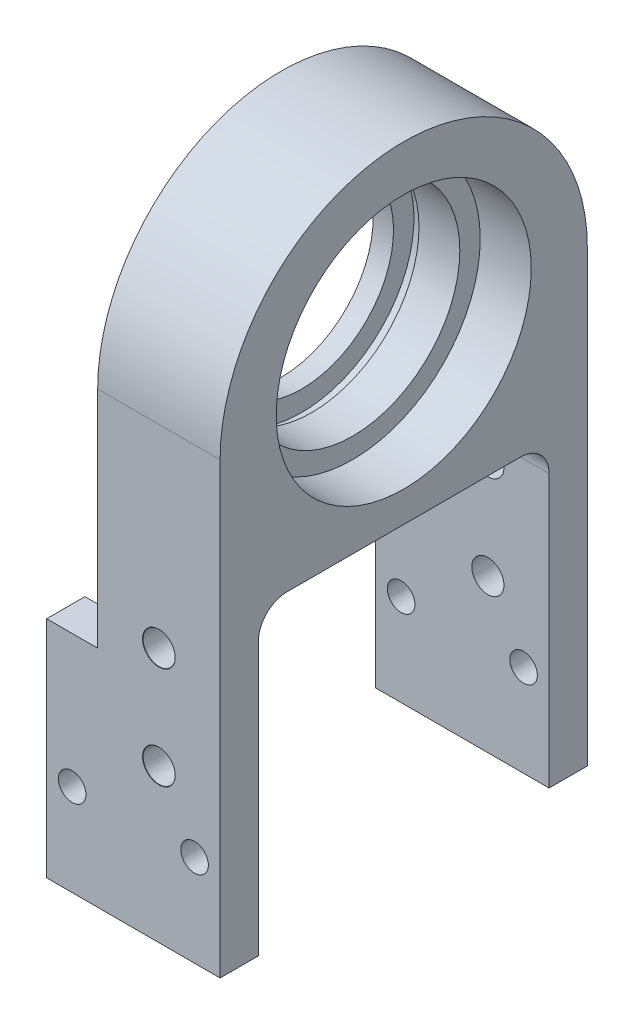
SolidWorks part; units mm, degrees
material "6061 Alloy"
ref_plane "Front Plane" through (0, 0, 0) normal (0, 0, 1) x (1, 0, 0)
ref_plane "Top Plane" through (0, 0, 0) normal (0, 1, 0) x (1, 0, 0)
ref_plane "Right Plane" through (0, 0, 0) normal (1, 0, 0) x (0, 0, -1)
sketch "Sketch1" plane through (0, 0, 0) normal (0, 0, 1) x (1, 0, 0)
  line L0 (0, 0) -> (17, 0)
  line L1 (17, 0) -> (17, 29)
  line L3 (17, 29) -> (17, 62)
  line L4 (17, 62) -> (5, 62)
  line L5 (5, 62) -> (5, 22)
  line L6 (5, 22) -> (0, 22)
  line L7 (0, 22) -> (0, 0)
  dimension "D1" = 17
  dimension "D2" = 62
  dimension "D3" = 22
  dimension "D4" = 12
extrude "Boss-Extrude1" add sketch "Sketch1" along normal blind 36
sketch "Sketch2" plane through (17, 0, 0) normal (1, 0, 0) x (0, 0, -1)
  line L0 (-18, 62) -> (-18, 12.1467) construction
  line L1 (-36, 62) -> (0, 62) construction
  circle A0 centre (-18, 45) radius 10.5
  dimension "D1" = 21
  dimension "D2" = 17
extrude "Cut-Extrude1" cut sketch "Sketch2" against normal through all
sketch "Sketch3" plane through (17, 0, 0) normal (1, 0, 0) x (0, 0, -1)
  line L0 (-36, 0) -> (0, 0) construction
  line L1 (-32.25, 0) -> (-3.75, 0)
  line L2 (-32.25, 0) -> (-32.25, 29.5)
  line L3 (-32.25, 29.5) -> (-3.75, 29.5)
  line L4 (-3.75, 0) -> (-3.75, 29.5)
  line L6 (-18, 0) -> (-18, 45) construction
  dimension "D1" = 28.5
  dimension "D2" = 29.5
extrude "Cut-Extrude2" cut sketch "Sketch3" against normal through all
sketch "Sketch6" plane through (5, 0, 0) normal (-1, 0, 0) x (0, 0, 1)
  circle A0 centre (18, 45) radius 10.5 construction
  circle A1 centre (18, 45) radius 10.5
  circle A2 centre (18, 45) radius 9
  dimension "D1" = 1.5
extrude "Boss-Extrude2" add sketch "Sketch6" against normal blind 2
sketch "Sketch10" plane through (5, 0, 0) normal (-1, 0, 0) x (0, 0, 1)
  circle A0 centre (18, 45) radius 11
  circle A1 centre (18, 45) radius 15
  dimension "D1" = 22
  dimension "D2" = 30
extrude "Cut-Extrude4" cut sketch "Sketch10" against normal blind 0.6
sketch "Sketch11" plane through (17, 0, 0) normal (1, 0, 0) x (0, 0, -1)
  circle A0 centre (-18, 45) radius 12.5
  dimension "D1" = 25
extrude "Cut-Extrude5" cut sketch "Sketch11" against normal blind 5
sketch "Sketch14" plane through (0, 0, 36) normal (0, 0, 1) x (1, 0, 0)
  line L0 (2.5, 9) -> (14.5, 9)
  line L3 (8.5, 9) -> (8.5, 0)
  line L4 (0, 0) -> (17, 0) construction
  line L6 (17, 32.5) -> (17, 57.5) construction
  line L7 (17, 32.5) -> (17, 57.5) construction
  point P0 (14.5, 9)
  point P2 (2.5, 9)
  point P25 (17, 45)
  dimension "D1" = 36
  dimension "D2" = 12
hole_wizard "M2.5 Clearance Hole1" positions "Sketch14" profile "Sketch13" hole size "M2.5" standard "DIN" end condition through all
sketch "Sketch13" plane through (14.5, 9, 36) normal (1, 0, 0) x (0, -1, 0)
  line L0 (0, 0) -> (0, 36)
  line L1 (0, 36) -> (1.35, 36)
  line L2 (1.35, 36) -> (1.35, 0)
  line L5 (1.35, 0) -> (0, 0)
  line L11 (0, -6.35) -> (0, 107.95) construction
  dimension "Thru Hole Dia." = 2.7
  dimension "Thru Hole Depth" = 36
sketch "Sketch15" plane through (0, 0, 0) normal (0, 0, -1) x (-1, 0, 0)
  line L0 (-14.5, 9) -> (-14.5, 3) construction
  line L1 (-13.15, 9) -> (-13.15, 3)
  line L2 (-15.85, 9) -> (-15.85, 3)
  line L3 (-2.5, 9) -> (-2.5, 3) construction
  line L4 (-1.15, 9) -> (-1.15, 3)
  line L5 (-3.85, 9) -> (-3.85, 3)
  arc A0 (-13.15, 9) -> (-15.85, 9) centre (-14.5, 9) ccw
  arc A1 (-15.85, 3) -> (-13.15, 3) centre (-14.5, 3) ccw
  arc A2 (-1.15, 9) -> (-3.85, 9) centre (-2.5, 9) ccw
  arc A3 (-3.85, 3) -> (-1.15, 3) centre (-2.5, 3) ccw
  circle A4 centre (-14.5, 9) radius 1.35 construction
  point P3 (-14.5, 6)
  point P8 (-2.5, 6)
  dimension "D1" = 6
extrude "Cut-Extrude6" [suppressed] cut sketch "Sketch15" against normal through all
sketch "Sketch16" plane through (0, 0, 0) normal (0, 0, -1) x (-1, 0, 0)
  line L0 (0, 22) -> (-5, 32)
  line L1 (-5, 62) -> (-5, 22) construction
  dimension "D1" = 10
rib "Rib6" [suppressed] sketch "Sketch16" sketch "Sketch16" thickness 3.75 extrusion direction parallel to sketch draft on no parameters "D1"=3.75
sketch "Sketch17" plane through (17, 0, 0) normal (1, 0, 0) x (0, 0, -1)
  line L1 (-36, 62) -> (0, 62)
  line L2 (-36, 62) -> (-36, 45)
  line L3 (-36, 45) -> (0, 45)
  line L4 (0, 62) -> (0, 45)
  circle A0 centre (-18, 45) radius 18
  line M9 (0, 0) -> (0, 62)
  line M10 (0, 62) -> (-36, 62)
  line M11 (-36, 62) -> (-36, 0)
extrude "Cut-Extrude7" cut sketch "Sketch17" against normal through all contours A0 M10 M11 | A0 M9 M10 region at (17, 58.082, 32.7544) region at (17, 58.082, 3.2456)
sketch "Sketch18" plane through (7, 0, 0) normal (1, 0, 0) x (0, 0, -1)
  circle A0 centre (-18, 45) radius 9 construction
  circle A1 centre (-18, 45) radius 9
  circle A2 centre (-18, 45) radius 9.4
  dimension "D1" = 0.4
extrude "Boss-Extrude3" [suppressed] add sketch "Sketch18" along normal up to surface (10 mm away) up to face at (17, 45, 5.5)
sketch "Sketch19" plane through (12, 0, 0) normal (1, 0, 0) x (0, 0, -1)
  circle A0 centre (-18, 45) radius 10.5 construction
  circle A1 centre (-18, 45) radius 10.5
  circle A2 centre (-18, 45) radius 10.9
  dimension "D1" = 0.4
extrude "Boss-Extrude4" [suppressed] add sketch "Sketch19" along normal up to surface (5 mm away) up to face at (17, 45, 5.5)
sketch "Sketch22" plane through (0, 0, 36) normal (0, 0, 1) x (1, 0, 0)
  line L0 (11, 45) -> (11, -8.6789) construction
  line L1 (5, 45) -> (17, 45) construction
  line L2 (0, 0) -> (17, 0) construction
  point P7 (11, 25)
  point P9 (11, 15)
  dimension "D1" = 10
  dimension "D2" = 15
hole_wizard "Tap Drill for M3 Helicoil1" positions "Sketch22" profile "Sketch21" hole size "M3x0.5" standard "DIN" end condition through all
sketch "Sketch21" plane through (11, 15, 36) normal (1, 0, 0) x (0, -1, 0)
  line L0 (0, 0) -> (0, 36)
  line L1 (0, 36) -> (1.575, 36)
  line L2 (1.575, 36) -> (1.575, 0.025)
  line L3 (1.575, 0.025) -> (1.6, 0)
  line L5 (1.6, 0) -> (0, 0)
  line L6 (-1.575, 0.025) -> (-1.6, 0) construction
  line L11 (0, -6.35) -> (0, 107.95) construction
  dimension "Thru Hole Dia." = 3.15
  dimension "Thru Hole Depth" = 36
  dimension "Near C'Sink Dia." = 3.2
  dimension "Near C'Sink Angle" = 90
sketch "Sketch23" plane through (17, 0, 0) normal (1, 0, 0) x (0, 0, -1)
  line L0 (-36, 0) -> (-36, 45) construction
  line L1 (0, 0) -> (0, 45) construction
  line L2 (-23.9161, 62) -> (-12.0839, 62) construction
  line L13 (-36, 45) -> (-36, 0)
  line L14 (-36, 0) -> (-32.25, 0)
  line L15 (-32.25, 0) -> (-32.25, 29.5)
  line L17 (-32.25, 29.5) -> (-3.75, 29.5)
  line L19 (-3.75, 29.5) -> (-3.75, 0)
  line L20 (-3.75, 0) -> (0, 0)
  line L21 (0, 0) -> (0, 45)
  line L22 (-12.0839, 62) -> (-23.9161, 62)
  line L23 (-36, 45) -> (-36, 0)
  line L24 (-36, 0) -> (-32.25, 0)
  line L25 (-32.25, 0) -> (-32.25, 29.5)
  line L27 (-32.25, 29.5) -> (-3.75, 29.5)
  line L29 (-3.75, 29.5) -> (-3.75, 0)
  line L30 (-3.75, 0) -> (0, 0)
  line L31 (0, 0) -> (0, 45)
  line L32 (-12.0839, 62) -> (-23.9161, 62)
  circle A0 centre (-18, 44) radius 18
  arc A3 (-23.9161, 62) -> (-36, 45) centre (-18, 45) ccw
  arc A4 (0, 45) -> (-12.0839, 62) centre (-18, 45) ccw
  arc A5 (-23.9161, 62) -> (-36, 45) centre (-18, 45) ccw
  arc A6 (0, 45) -> (-12.0839, 62) centre (-18, 45) ccw
  arc M15 (-23.9161, 62) -> (-36, 45) centre (-18, 45) ccw
  line M16 (-36, 45) -> (-36, 0)
  arc M25 (0, 45) -> (-12.0839, 62) centre (-18, 45) ccw
  line M26 (-12.0839, 62) -> (-23.9161, 62)
  dimension "D1" = 0
extrude "Cut-Extrude8" cut sketch "Sketch23" against normal through all contours A0 L32 M15 M16 | A0 L31 M25 M26 region at (17, 55.2811, 32.4637) region at (17, 61.9745, 15.042)
sketch "Sketch24" plane through (5, 0, 0) normal (-1, 0, 0) x (0, 0, 1)
  line L0 (3.75, 29.5) -> (32.25, 29.5) construction
  line L1 (13, 29.5) -> (23, 29.5)
  line L2 (13, 29.5) -> (13, 30.8579)
  line L3 (13, 30.8579) -> (23, 30.8579)
  line L4 (23, 29.5) -> (23, 30.8579)
  circle A0 centre (18, 45) radius 15 construction
  dimension "D1" = 10
extrude "Cut-Extrude10" cut sketch "Sketch24" against normal up to surface (0.6 mm away) up to face at (5.6, 34, 18)
fillet "Fillet1" radius 4 2 edges at (5.3, 30.8579, 23) (5.3, 30.8579, 13)
fillet "Fillet2" radius 2.8 2 edges at (11, 29.5, 32.25) (11, 29.5, 3.75)
ref_plane "Plane1" through (0, 0, 18) normal (0, 0, -1) x (-1, 0, 0)
sketch "Sketch25" plane through (0, 0, 18) normal (0, 0, -1) x (-1, 0, 0)
  line L0 (-7, 34.5) -> (-7, 34)
  line L1 (-7, 55.5) -> (-7, 34.5) construction
  line L2 (-7, 34) -> (-8, 34)
  line L3 (-8, 34) -> (-8, 34.5)
  line L4 (-8, 34.5) -> (-7, 34.5)
  line L5 (-5, 45) -> (-19.1096, 45) construction
  line L6 (-5, 36) -> (-5, 54) construction
  dimension "D1" = 1
  dimension "D2" = 0.5
revolve "Cut-Revolve1" cut sketch "Sketch25" angle 360 about L5
